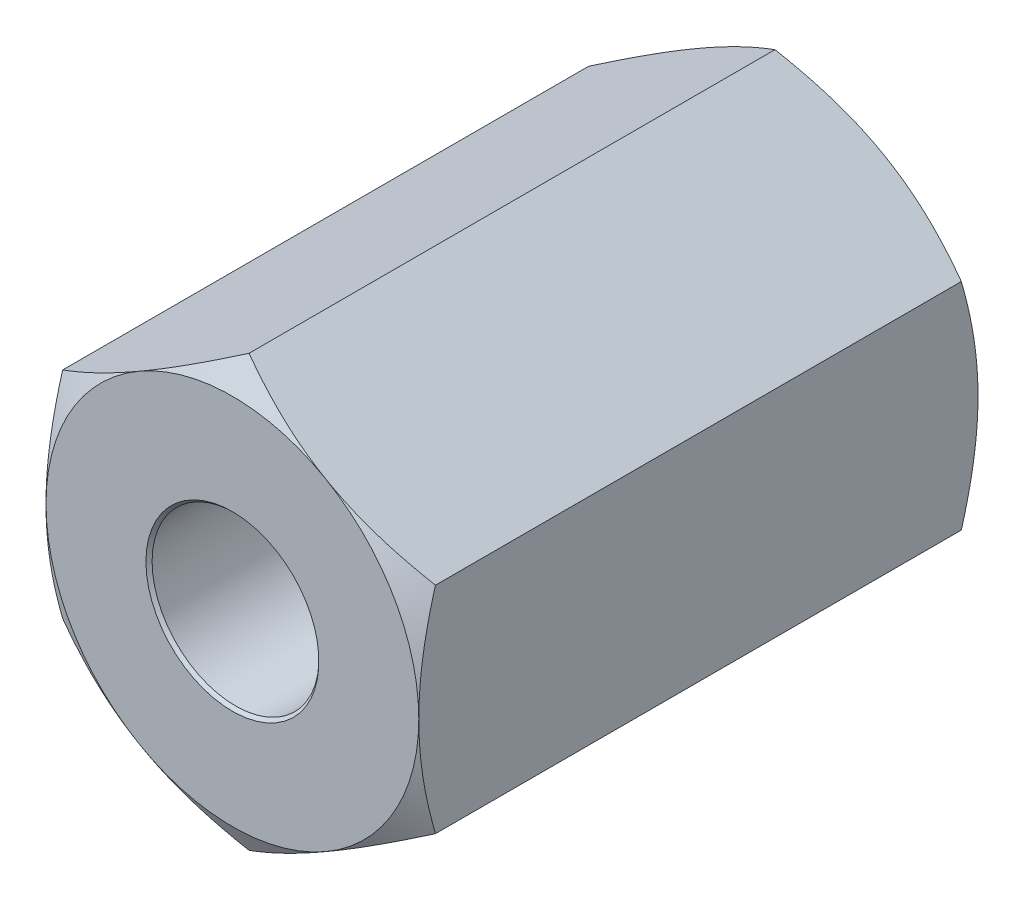
SolidWorks part; units mm, degrees
ref_plane "Front Plane" through (0, 0, 0) normal (0, 0, 1) x (1, 0, 0)
ref_plane "Top Plane" through (0, 0, 0) normal (0, 1, 0) x (1, 0, 0)
ref_plane "Right Plane" through (0, 0, 0) normal (1, 0, 0) x (0, 0, -1)
sketch "Sketch3" plane through (0, 0, 0) normal (1, 0, 0) x (0, 0, -1)
  line L0 (-4.7625, 0) -> (4.7625, 0) construction
  line L1 (0, 3.175) -> (0, -3.175) construction
  line L2 (-4.7625, 1.4224) -> (-4.7625, -1.4224) construction
  point P2 (0, 0)
  point P3 (0, 0)
  dimension "D1" = 4.7625
  dimension "Length" = 9.525
  dimension "Min Thread Length" = 4.7625
  dimension "Thread Dia" = 2.8448
  dimension "Hex" = 6.35
sketch "Sketch1" plane through (0, 0, 0) normal (0, 0, 1) x (1, 0, 0)
  line L1 (0, 3.6662) -> (-3.175, 1.8331)
  line L2 (-3.175, 1.8331) -> (-3.175, -1.8331)
  line L3 (-3.175, -1.8331) -> (0, -3.6662)
  line L4 (0, -3.6662) -> (3.175, -1.8331)
  line L5 (3.175, -1.8331) -> (3.175, 1.8331)
  line L6 (3.175, 1.8331) -> (0, 3.6662)
  circle A0 centre (0, 0) radius 3.175 construction
  circle A1 centre (0, 0) radius 1.4224
extrude "Extrude1" add sketch "Sketch1" along normal up to vertex (4.7625 mm away) and the other way up to vertex (4.7625 mm away) up to point (0, 0, 4.7625) other way up to point (0, 0, -4.7625)
sketch "Sketch11" plane through (0, 0, -4.7625) normal (0, 0, -1) x (-1, 0, 0)
  circle A0 centre (0, 0) radius 1.4224 construction
  circle A1 centre (0, 0) radius 1.4224
curve "Helix/Spiral1" pitch 0.635 height 10.16 turns 16 parameters "Pitch"=0.635
sketch "Sketch12" plane through (0, 0, 0) normal (1, 0, 0) x (0, 0, -1)
  line L0 (5.3181, 1.4224) -> (4.7625, 1.4224)
  line L1 (5.3181, 1.4224) -> (5.08, 1.01)
  line L2 (5.08, 1.01) -> (5.0006, 1.01)
  line L3 (5.0006, 1.01) -> (4.7625, 1.4224)
  line L4 (5.0403, 1.01) -> (5.0403, 1.4224) construction
  line L5 (5.1991, 1.2162) -> (4.8816, 1.2162) construction
  dimension "D1" = 0.0794
  dimension "D2" = 0.3175
  dimension "D3" = 60
sweep "Sweep1" [suppressed] add profiles "Sketch12" path "Helix/Spiral1"
sketch "Sketch6" plane through (0, 0, -4.7625) normal (0, 0, -1) x (-1, 0, 0)
  line L6 (0, 3.6662) -> (-3.175, 1.8331)
  line L7 (-3.175, 1.8331) -> (-3.175, -1.8331)
  line L8 (-3.175, -1.8331) -> (0, -3.6662)
  line L9 (0, -3.6662) -> (3.175, -1.8331)
  line L10 (3.175, -1.8331) -> (3.175, 1.8331)
  line L11 (3.175, 1.8331) -> (0, 3.6662)
  line L12 (0, 3.6662) -> (-3.175, 1.8331)
  line L13 (-3.175, 1.8331) -> (-3.175, -1.8331)
  line L14 (-3.175, -1.8331) -> (0, -3.6662)
  line L15 (0, -3.6662) -> (3.175, -1.8331)
  line L16 (3.175, -1.8331) -> (3.175, 1.8331)
  line L17 (3.175, 1.8331) -> (0, 3.6662)
  dimension "D1" = 0
extrude "Extrude2" [suppressed] cut sketch "Sketch6" along normal through all
sketch "Sketch7" plane through (0, 0, -4.7625) normal (0, 0, -1) x (-1, 0, 0)
  circle A2 centre (0, 0) radius 1.4732
  circle A3 centre (0, 0) radius 1.4732
  dimension "D1" = 0.0508
extrude "Extrude3" cut sketch "Sketch7" against normal through all draft 43
sketch "Sketch8" plane through (0, 0, -4.7625) normal (0, 0, -1) x (-1, 0, 0)
  circle A0 centre (0, 0) radius 3.175 construction
  circle A1 centre (0, 0) radius 3.175
extrude "Extrude4" cut sketch "Sketch8" against normal through all draft 60 flip side to cut
mirror "Mirror1" about plane through (0, 0, 0) normal (0, 0, 1) of "Extrude2", "Extrude3", "Extrude4"
sketch "Sketch9" [suppressed] plane through (0, 0, 0) normal (1, 0, 0) x (0, 0, -1)
  line L1 (-1.5875, 0.8128) -> (1.5875, 0.8128)
  line L2 (-1.5875, 0.8128) -> (-1.5875, 0)
  line L3 (-1.5875, 0) -> (1.5875, 0)
  line L4 (1.5875, 0.8128) -> (1.5875, 0)
  line L7 (-6.35, 0) -> (6.35, 0) construction
revolve "Revolve" [suppressed] add sketch "Sketch9" angle 360 about L0
sketch "Sketch10" [suppressed] plane through (0, 0, 0) normal (1, 0, 0) x (0, 0, -1)
  line L0 (6.35, 0.762) -> (1.5875, 0.762)
  line L1 (-6.35, 0.762) -> (-1.5875, 0.762)
  line L2 (1.5875, 0.762) -> (1.5875, -0.762)
  line L3 (-6.35, -0.8128) -> (-1.5875, -0.8128)
  line L4 (-1.5875, 0.762) -> (-1.5875, -0.8128)
  line L5 (1.5875, -0.762) -> (6.35, -0.762)
equation "\"D1@Sketch3\" = \"Min Thread Length@Sketch3\""
equation "\"D3@Helix/Spiral1\" = \"Length@Sketch3\"+\"Pitch@Helix/Spiral1\""
equation "\"D1@Sketch12\" = \"Pitch@Helix/Spiral1\"*.125"
equation "\"D2@Sketch12\" = \"Pitch@Helix/Spiral1\"*.5"
